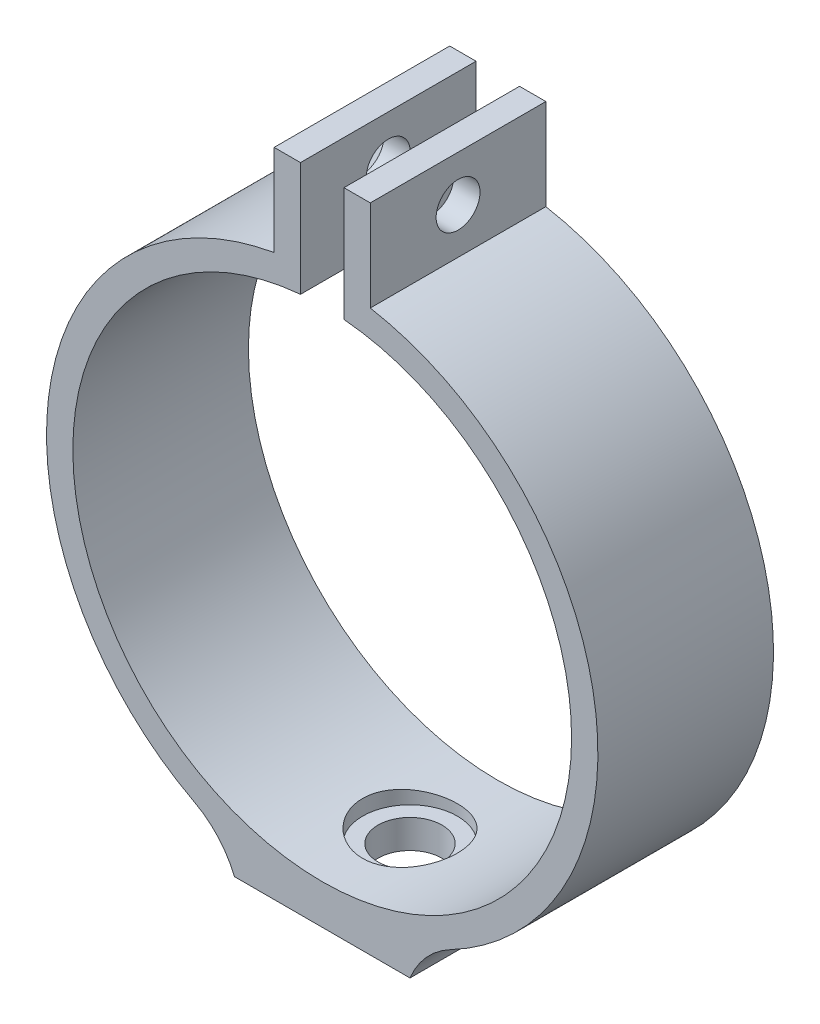
SolidWorks part; units mm, degrees
ref_plane "Front Plane" through (0, 0, 0) normal (0, 0, 1) x (1, 0, 0)
ref_plane "Top Plane" through (0, 0, 0) normal (0, 1, 0) x (1, 0, 0)
ref_plane "Right Plane" through (0, 0, 0) normal (1, 0, 0) x (0, 0, -1)
sketch "Sketch2" plane through (0, 0, 0) normal (0, 0, 1) x (1, 0, 0)
  line L0 (-2.4757, 28.2969) -> (-2.3532, 26.8973) construction
  line L1 (2.4757, 28.2969) -> (2.3532, 26.8973) construction
  line L2 (0, 0) -> (0, -28.405) construction
  line L3 (0, -28.405) -> (0, -32.905) construction
  line L5 (-10, -29.7704) -> (-10, -32.905)
  line L6 (-10, -32.905) -> (10, -32.905)
  line L7 (10, -29.7704) -> (10, -32.905)
  line L8 (-15.9139, -27.0744) -> (10, -32.905) construction
  line L9 (-10, -32.905) -> (11.2682, -28.1197) construction
  line L10 (2.4757, 28.2969) -> (2.4757, 41.2969)
  line L11 (2.4757, 41.2969) -> (5.4757, 41.2969)
  line L12 (5.4757, 41.2969) -> (5.4757, 30.924)
  line L13 (-2.4757, 28.2969) -> (-2.4757, 41.2969)
  line L14 (-2.4757, 41.2969) -> (-5.4757, 41.2969)
  line L15 (-5.4757, 41.2969) -> (-5.4757, 30.924)
  arc A0 (-2.4757, 28.2969) -> (2.4757, 28.2969) centre (0, 0) ccw
  arc A1 (-5.4757, 30.924) -> (-10, -29.7704) centre (0, 0) ccw
  arc A2 (10, -29.7704) -> (5.4757, 30.924) centre (0, 0) ccw
  point P11 (0, -30.655)
  dimension "D1" = 56.81
  dimension "D2" = 3
  dimension "D3" = 175
  dimension "D4" = 175
  dimension "D5" = 20
  dimension "D6" = 4.5
  dimension "D7" = 3
  dimension "D8" = 13
  dimension "D9" = 3
  dimension "D10" = 13
extrude "Boss-Extrude1" add sketch "Sketch2" along normal blind 20
fillet "Fillet1" radius 10 2 edges at (10, -29.7704, 10) (-10, -29.7704, 10)
ref_plane "Plane1" through (0, -28.405, 0) normal (0, 1, 0) x (1, 0, 0)
sketch "Sketch3" plane through (0, -28.405, 0) normal (0, 1, 0) x (1, 0, 0)
  line L0 (0, 0) -> (0, -20) construction
  line L1 (-28.405, -20) -> (28.405, -20) construction
  circle A1 centre (0, -10) radius 5.4
  dimension "D1" = 10.8
extrude "Cut-Extrude3" cut sketch "Sketch3" against normal offset from surface 3.27 and the other way blind 20 up to face at (0, -32.905, 10)
sketch "Sketch4" plane through (0, -29.635, 0) normal (0, 1, 0) x (1, 0, 0)
  circle A0 centre (0, -10) radius 3.64
  dimension "D1" = 7.28
extrude "Cut-Extrude4" cut sketch "Sketch4" against normal through all
sketch "Sketch5" plane through (-5.4757, 0, 0) normal (-1, 0, 0) x (0, 0, 1)
  line L0 (0, 41.2969) -> (20, 30.924) construction
  line L1 (0, 30.924) -> (20, 41.2969) construction
  circle A0 centre (10, 36.1104) radius 2.5
  dimension "D1" = 5
extrude "Cut-Extrude5" cut sketch "Sketch5" against normal through all
